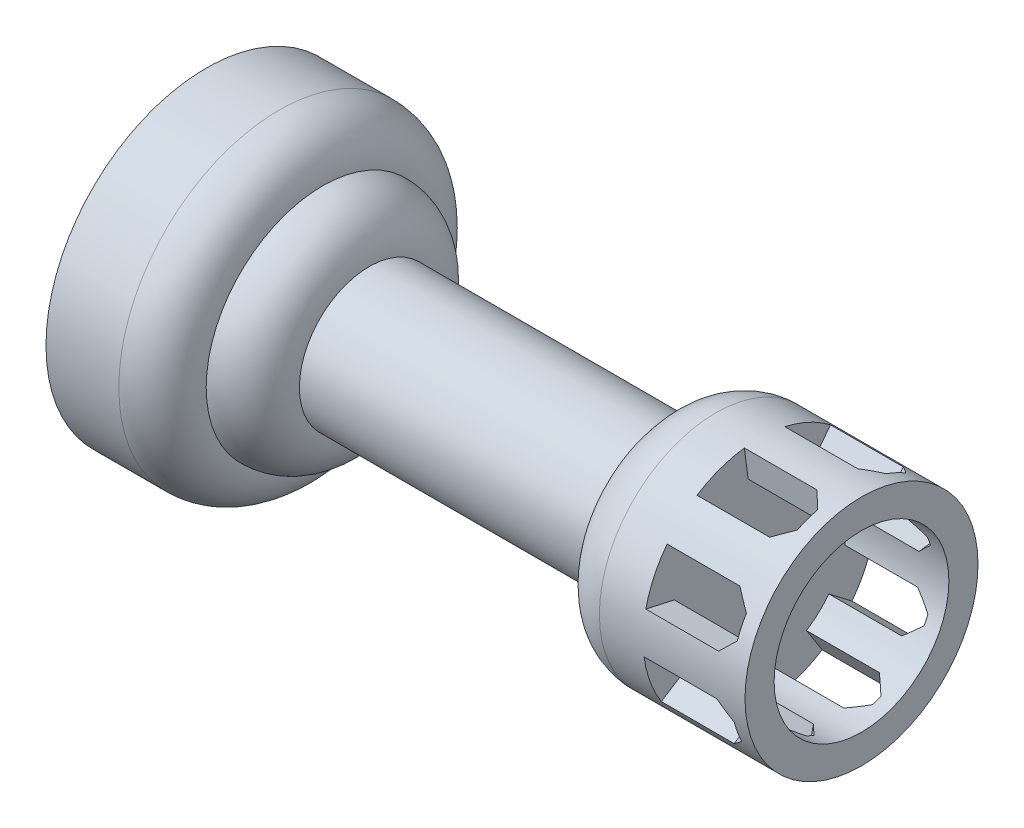
SolidWorks part; units mm, degrees
ref_plane "Спереди" through (0, 0, 0) normal (0, 0, 1) x (1, 0, 0)
ref_plane "Сверху" through (0, 0, 0) normal (0, 1, 0) x (1, 0, 0)
ref_plane "Справа" through (0, 0, 0) normal (1, 0, 0) x (0, 0, -1)
other "Configuration Table"
sketch "Эскиз1" plane through (0, 0, 0) normal (0, 1, 0) x (1, 0, 0)
  line L0 (0, 11) -> (38, 11) construction
  line L1 (0, 22) -> (5, 22)
  line L2 (0, 22) -> (0, 0)
  line L3 (0, 0) -> (5, 0)
  line L4 (5, 22) -> (5, 0)
  line L5 (5, 19) -> (8, 19)
  line L6 (5, 19) -> (5, 3)
  line L7 (5, 3) -> (8, 3)
  line L8 (8, 19) -> (8, 3)
  line L9 (8, 15.8) -> (35, 15.8)
  line L10 (8, 15.8) -> (8, 6.2)
  line L11 (8, 6.2) -> (35, 6.2)
  line L12 (35, 15.8) -> (35, 6.2)
  line L13 (35, 3) -> (38, 3)
  line L14 (35, 3) -> (35, 19)
  line L15 (35, 19) -> (38, 19)
  line L16 (38, 3) -> (38, 19)
  line L24 (38, 3) -> (45, 3)
  line L25 (38, 3) -> (38, 5)
  line L26 (38, 5) -> (45, 5)
  line L27 (45, 3) -> (45, 5)
  arc A0 (35, 3) -> (31.4652, 6.2) centre (35, 6.5523) cw
  arc A1 (8, 3) -> (11.2, 6.2) centre (8, 6.2) ccw
  arc A2 (5, 0) -> (8, 3) centre (5, 3) ccw
  dimension "D13" = 3.5523
  dimension "D14" = 7
  dimension "D15" = 3.2
  dimension "D17" = 3
  dimension "D1" = 22
  dimension "D2" = 5
  dimension "D3" = 3
  dimension "D4" = 3
  dimension "D5" = 3
  dimension "D6" = 27
  dimension "D7" = 3.2
  dimension "D8" = 3.2
  dimension "D9" = 3.2
  dimension "D10" = 3.2
  dimension "D11" = 3
  dimension "D12" = 16
  dimension "D16" = 2
revolve "Повернуть11" add sketch "Эскиз1" angle 360 about L0 region at (2.5, 0, -5.5) region at (6.5, 0, -7) region at (21.5, 0, -8.6) region at (36.5, 0, -7) region at (9.3581, 0, -4.8419) region at (33.5307, 0, -4.8526) region at (41.5, 0, -4)
sketch "Эскиз2" plane through (0, 0, 0) normal (-1, 0, 0) x (0, 0, 1)
  line L0 (50, 0) -> (-50, 0) construction
  line L1 (-22, 0) -> (0, 0) construction
  circle A0 centre (-11, 0) radius 10
  circle A1 centre (-11, 0) radius 11 construction
  dimension "D1" = 20
extrude "Вырез-Вытянуть1" cut sketch "Эскиз2" along direction (-1, 0, 0) on the side against the normal blind 2.5
sketch "Эскиз6" plane through (38, 0, 0) normal (1, 0, 0) x (0, 0, -1)
  line L0 (11, 0) -> (3.1896, 1.7315) construction
  line L1 (11, 0) -> (4.6532, 4.8701) construction
  line L2 (50, 0) -> (-50, 0) construction
  line L3 (4.6532, 4.8701) -> (6.2399, 3.6526)
  line L4 (3.1896, 1.7315) -> (5.1422, 1.2986)
  circle A2 centre (11, 0) radius 8 construction
  arc A5 (3.1896, 1.7315) -> (4.6532, 4.8701) centre (11, 0) cw
  arc A6 (5.1422, 1.2986) -> (6.2399, 3.6526) centre (11, 0) cw
  circle A8 centre (11, 0) radius 6 construction
  dimension "D1" = 12.5
  dimension "D2" = 25
extrude "Вырез-Вытянуть2" cut sketch "Эскиз6" along normal blind 6
sketch "Эскиз7" plane through (0, 0, 0) normal (1, 0, 0) x (0, 0, -1)
  line L0 (3, 0) -> (19, 0) construction
  line L1 (50, 0) -> (-50, 0) construction
  circle A0 centre (11, 0) radius 8 construction
pattern_circular "Круговой массив1" count 8 over 360 about axis through (45, 0, -11) along (-1, 0, 0) of "Вырез-Вытянуть2"
revolve "Повернуть12" add sketch "Эскиз1<12>" angle 360 about L0 region at (6.2732, 0, -1.7268)
sketch "Эскиз1<12>" plane through (0, 0, 0) normal (0, 1, 0) x (1, 0, 0) same geometry as "Эскиз1"
chamfer "Фаска4" distance 1 angle 45 2 edges at (44, 3.7611, -16.9037) (44, 0.9137, -17.9401)
chamfer "Фаска5" distance 1 angle 45 2 edges at (44, 5.5535, -15.2613) (44, 6.8341, -12.5151)
chamfer "Фаска6" distance 1 angle 45 12 edges at (44, -1.5151, -17.8341) (44, -4.2613, -16.5535) (44, -6.9401, -11.9137) (44, -5.9037, -14.7611) (44, -6.8341, -9.4849) (44, -5.5535, -6.7387) (44, -3.7611, -5.0963) (44, -0.9137, -4.0599) (44, 1.5151, -4.1659) (44, 4.2613, -5.4465) (44, 5.9037, -7.2389) (44, 6.9401, -10.0863)
sketch "Эскиз3" plane through (53, 0, 0) normal (1, 0, 0) x (0, 0, -1)
  line L0 (17, 0) -> (5, 0) construction
  line L1 (11, 0) -> (13.0706, 7.7274) construction
  line L2 (11, 0) -> (16.1423, 6.1284) construction
  line L3 (13.0706, 7.7274) -> (12.5529, 5.7956)
  line L4 (16.1423, 6.1284) -> (14.8567, 4.5963)
  line L5 (11, 0) -> (11, 8) construction
  circle A0 centre (11, 0) radius 6 construction
  circle A1 centre (11, 0) radius 6 construction
  circle A2 centre (11, 0) radius 8 construction
  arc A3 (13.0706, 7.7274) -> (16.1423, 6.1284) centre (11, 0) cw
  arc A4 (12.5529, 5.7956) -> (14.8567, 4.5963) centre (11, 0) cw
  dimension "D1" = 15
  dimension "D2" = 25
